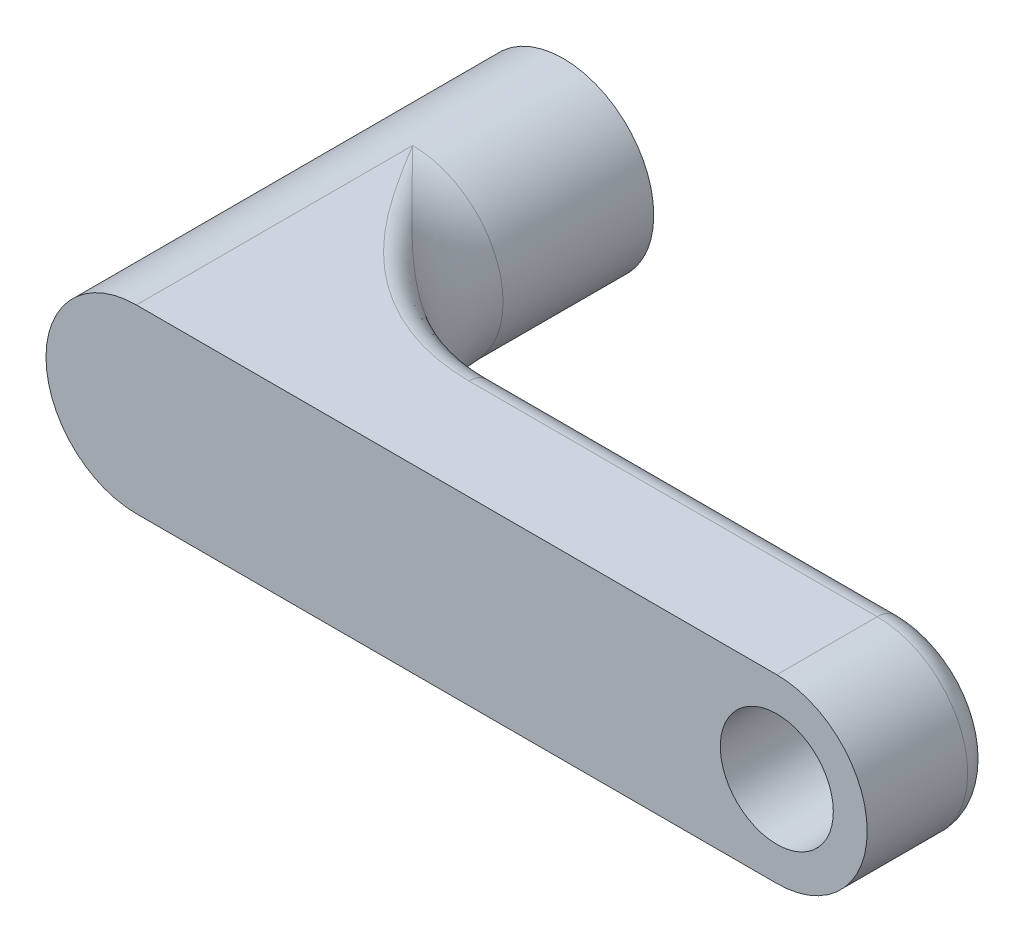
SolidWorks part; units mm, degrees
ref_plane "Front Plane" through (0, 0, 0) normal (0, 0, 1) x (1, 0, 0)
ref_plane "Top Plane" through (0, 0, 0) normal (0, 1, 0) x (1, 0, 0)
ref_plane "Right Plane" through (0, 0, 0) normal (1, 0, 0) x (0, 0, -1)
sketch "Sketch1" plane through (0, 0, 0) normal (0, 0, 1) x (1, 0, 0)
  circle A0 centre (0, 0) radius 3.6
  dimension "D1" = 7.2
extrude "Boss-Extrude1" add sketch "Sketch1" along normal blind 17 contours A0
sketch "Sketch2" plane through (0, 0, 0) normal (0, 0, -1) x (-1, 0, 0)
  circle A0 centre (0, 0) radius 2.125
  dimension "D1" = 4.25
extrude "Cut-Extrude1" cut sketch "Sketch2" against normal blind 10
sketch "Sketch3" plane through (0, 0, 17) normal (0, 0, 1) x (1, 0, 0)
  line L0 (0, -3.6) -> (25.5, -3.6)
  line L1 (25.5, -3.6) -> (25.5, 3.6)
  line L2 (25.5, 3.6) -> (0, 3.6)
  circle A0 centre (0, 0) radius 3.6 construction
  circle A1 centre (0, 0) radius 3.6 construction
  circle A2 centre (25.5, 0) radius 3.6
  circle M3 centre (0, 0) radius 3.6
  dimension "D1" = 25.5
extrude "Boss-Extrude2" add sketch "Sketch3" against normal blind 5 contours A2 L2 L0 M3 | L1 A2 | L1 A2 region at (12.75, 0, 17) region at (23.9721, 0, 17) region at (27.0279, 0, 17)
sketch "Sketch4" plane through (0, 0, 17) normal (0, 0, 1) x (1, 0, 0)
  circle A0 centre (25.5, 0) radius 2.25
  dimension "D1" = 4.5
extrude "Cut-Extrude2" cut sketch "Sketch4" against normal through all
fillet "Fillet1" radius 6 1 edges at (3.6, 0, 12)
fillet "Fillet2" radius 1 5 edges at (6.4994, 3.6, 11.5938) (29.1, 0, 12) (17.1997, 3.6, 12) (6.4994, -3.6, 11.5938) (17.1997, -3.6, 12)
